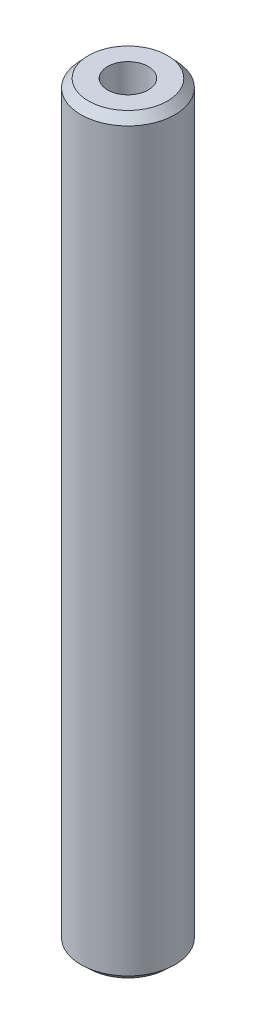
SolidWorks part; units mm, degrees
ref_plane "Front Plane" through (0, 0, 0) normal (0, 0, 1) x (1, 0, 0)
ref_plane "Top Plane" through (0, 0, 0) normal (0, 1, 0) x (1, 0, 0)
ref_plane "Right Plane" through (0, 0, 0) normal (1, 0, 0) x (0, 0, -1)
sketch "Sketch1" plane through (0, 0, 0) normal (0, 1, 0) x (1, 0, 0)
  circle A0 centre (0, 0) radius 10
  dimension "SHAFT_OD" = 20
extrude "Boss-Extrude1" add sketch "Sketch1" along normal blind 159.9684
sketch "Sketch2" plane through (0, 0, 0) normal (0, 1, 0) x (1, 0, 0)
  circle A0 centre (0, 0) radius 4.3337
  dimension "BORE_D" = 8.6674
extrude "Cut-Extrude1" cut sketch "Sketch2" along normal through all
chamfer "Chamfer1" distance 1.7283 angle 42.735 2 edges at (0, 159.9684, 10) (0, 0, 10) first distance on face at (0, 159.9684, 10) first distance on face at (0, 0, 4.3337)
